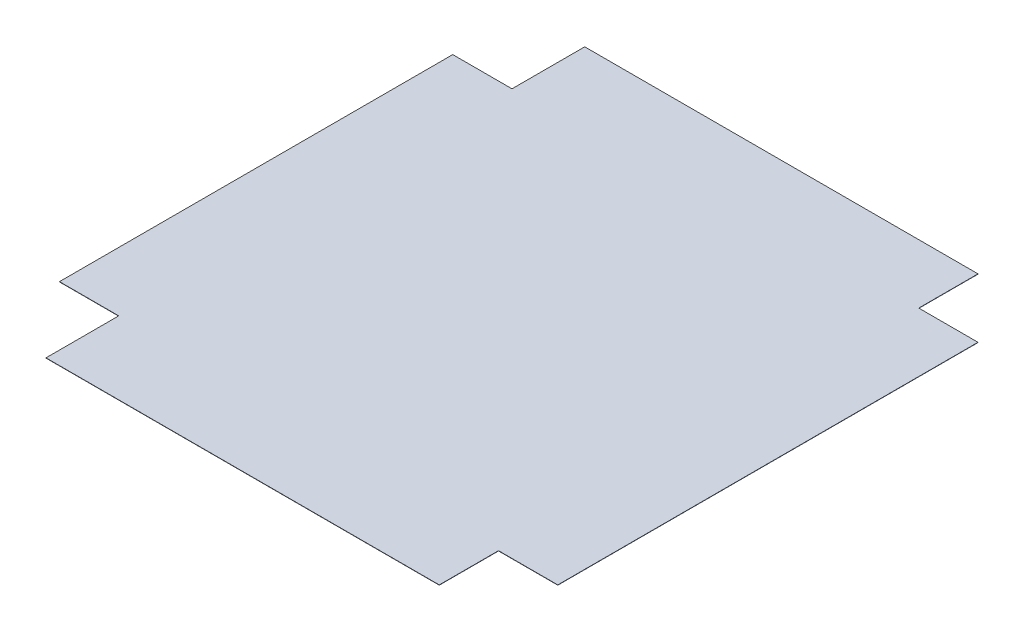
SolidWorks part; units mm, degrees
material "Corrugated Paper"
ref_plane "Front" through (0, 0, 0) normal (0, 0, 1) x (1, 0, 0)
ref_plane "Top" through (0, 0, 0) normal (0, 1, 0) x (1, 0, 0)
ref_plane "Right" through (0, 0, 0) normal (1, 0, 0) x (0, 0, -1)
ref_axis "X" through (-80.9, 0, 0) along (1, 0, 0)
ref_axis "Y" through (0, -50, 0) along (0, 1, 0)
ref_axis "Z" through (0, 0, -80.9) along (0, 0, 1)
sketch "Sketch1" plane through (0, 0, 0) normal (0, 1, 0) x (1, 0, 0)
  line L0 (-73, 100) -> (73, 100)
  line L1 (73, 100) -> (73, 78)
  line L2 (73, 78) -> (95, 78)
  line L3 (95, 78) -> (95, -78)
  line L4 (95, -78) -> (73, -78)
  line L5 (73, -78) -> (73, -100)
  line L6 (73, -100) -> (-73, -100)
  line L7 (-73, -100) -> (-73, -73)
  line L8 (-73, -73) -> (-95, -73)
  line L9 (-95, -73) -> (-95, 73)
  line L10 (-95, 73) -> (-73, 73)
  line L11 (-73, 73) -> (-73, 100)
  line L12 (-95, 0) -> (95, 0) construction
  line L13 (0, 100) -> (0, -100) construction
  dimension "D1" = 190
  dimension "D2" = 200
  dimension "D3" = 22
  dimension "D4" = 22
extrude "Boss-Extrude1" add sketch "Sketch1" along normal mid plane 0.1
